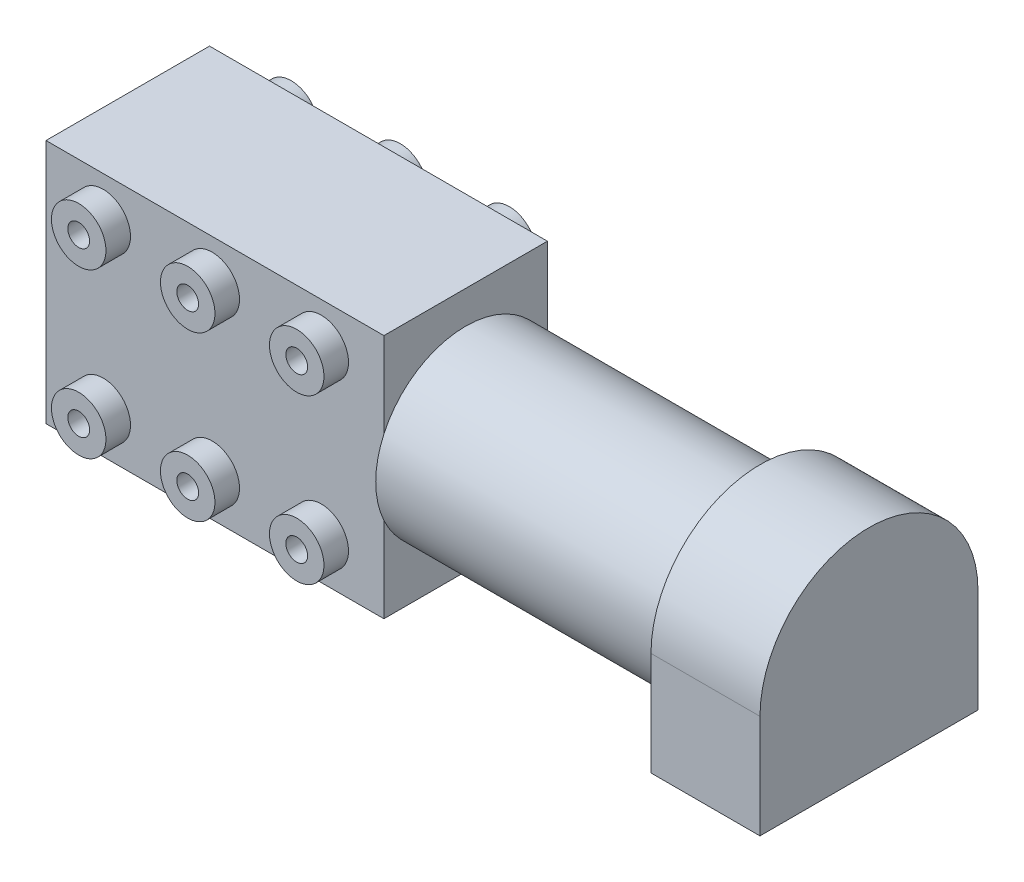
SolidWorks part; units mm, degrees
ref_plane "정면" through (0, 0, 0) normal (0, 0, 1) x (1, 0, 0)
ref_plane "윗면" through (0, 0, 0) normal (0, 1, 0) x (1, 0, 0)
ref_plane "우측면" through (0, 0, 0) normal (1, 0, 0) x (0, 0, -1)
ref_plane "평면1" through (0, 0, 10) normal (0, 0, 1) x (1, 0, 0)
sketch "스케치1" plane through (0, 0, 10) normal (0, 0, 1) x (1, 0, 0)
  line L1 (-31, 22.5) -> (31, 22.5)
  line L2 (-31, 22.5) -> (-31, -22.5)
  line L3 (-31, -22.5) -> (31, -22.5)
  line L4 (31, 22.5) -> (31, -22.5)
  line L5 (-31, 22.5) -> (31, -22.5) construction
  line L6 (-31, -22.5) -> (31, 22.5) construction
  point P0 (0, 0)
  dimension "D1" = 62
  dimension "D2" = 45
extrude "보스-돌출1" add sketch "스케치1" along normal blind 30
sketch "스케치2" plane through (31, 0, 0) normal (1, 0, 0) x (0, 0, -1)
  line L5 (-10, -22.5) -> (-10, 22.5) construction
  line L7 (-40, -22.5) -> (-10, -22.5) construction
  circle A0 centre (-25, 0) radius 16.5
  dimension "D1" = 33
  dimension "D2" = 15
  dimension "D3" = 22.5
extrude "보스-돌출2" add sketch "스케치2" along normal blind 52 contours A0
sketch "스케치4" plane through (83, 0, 0) normal (1, 0, 0) x (0, 0, -1)
  line L0 (-40, 6.8739) -> (-40, 22.5) construction
  line L1 (-43, 19.5) -> (-3, 19.5)
  line L2 (-43, 19.5) -> (-43, -19.5)
  line L3 (-43, -19.5) -> (-3, -19.5)
  line L4 (-3, 19.5) -> (-3, -19.5)
  line L5 (-43, 19.5) -> (-3, -19.5) construction
  line L6 (-43, -19.5) -> (-3, 19.5) construction
  point P0 (-23, 0)
  dimension "D1" = 17
  dimension "D2" = 39
  dimension "D3" = 40
  dimension "D4" = 0
extrude "보스-돌출4" add sketch "스케치4" along normal blind 20
sketch "스케치6" plane through (103, 0, 0) normal (1, 0, 0) x (0, 0, -1)
  line L2 (-43, 19.5) -> (-43, -19.5) construction
  line L3 (-3, -19.5) -> (-3, 19.5) construction
  line L4 (-3, 19.5) -> (-43, 19.5) construction
  line L5 (-43, -0.5) -> (-43, 19.5)
  line L6 (-43, 19.5) -> (-3, 19.5)
  line L7 (-3, 19.5) -> (-3, -0.5)
  arc A0 (-43, -0.5) -> (-3, -0.5) centre (-23, -0.5) cw
  line M1 (-3, -19.5) -> (-3, 19.5)
  line M2 (-3, 19.5) -> (-43, 19.5)
  line M3 (-43, 19.5) -> (-43, -19.5)
  dimension "D1" = 20
extrude "컷-돌출1" cut sketch "스케치6" against normal up to next contours A0 L6 M3 | A0 M2 M1 region at (103, 15.0326, 7.4674) region at (103, 15.0326, 38.5326)
sketch "스케치8" plane through (0, 0, 10) normal (0, 0, -1) x (-1, 0, 0)
  line L1 (-31, 22.5) -> (31, 22.5) construction
  line L2 (31, 22.5) -> (31, -22.5) construction
  circle A0 centre (20.5, -15) radius 5
  circle A1 centre (20.5, -15) radius 2
  circle A2 centre (12.5, 0) radius 6
  circle A8 centre (20.5, 15) radius 5
  circle A9 centre (20.5, 15) radius 2
  circle A14 centre (0.5, 15) radius 5
  circle A15 centre (0.5, 15) radius 2
  circle A16 centre (0.5, -15) radius 5
  circle A17 centre (0.5, -15) radius 2
  circle A18 centre (-19.5, 15) radius 5
  circle A19 centre (-19.5, 15) radius 2
  circle A20 centre (-19.5, -15) radius 5
  circle A21 centre (-19.5, -15) radius 2
  dimension "D1" = 4
  dimension "D2" = 10
  dimension "D3" = 30
  dimension "D4" = 7.5
  dimension "D5" = 8
  dimension "D6" = 18.5
  dimension "D7" = 4
  dimension "D8" = 10
  dimension "D9" = 8
  dimension "D10" = 12
  dimension "D11" = 22.5
  dimension "D12" = 3
extrude "보스-돌출6" add sketch "스케치8" along normal blind 4.5 contours A16 A17 | A20 A21 | A0 A1 | A8 A9 | A14 A15 | A18 A19 region at (-15.6414, -15, 10) region at (-15.6414, 15, 10) region at (4.3586, 15, 10) region at (4.3586, -15, 10) region at (24.3586, 15, 10) region at (24.3586, -15, 10)
ref_plane "평면2" through (0, 0, 25) normal (0, 0, -1) x (-1, 0, 0)
mirror "대칭 복사1" about plane through (0, 0, 25) normal (0, 0, -1) of "보스-돌출6"
extrude "보스-돌출7" add sketch "스케치8<3>" along normal blind 4.5 contours A2 region at (-12.5, 0, 10)
sketch "스케치8<3>" plane through (0, 0, 10) normal (0, 0, -1) x (-1, 0, 0) same geometry as "스케치8"
sketch "스케치9" plane through (0, 0, 5.5) normal (0, 0, -1) x (-1, 0, 0)
  circle A0 centre (12.5, 0) radius 4
  dimension "D1" = 8
extrude "컷-돌출2" cut sketch "스케치9" against normal blind 10
